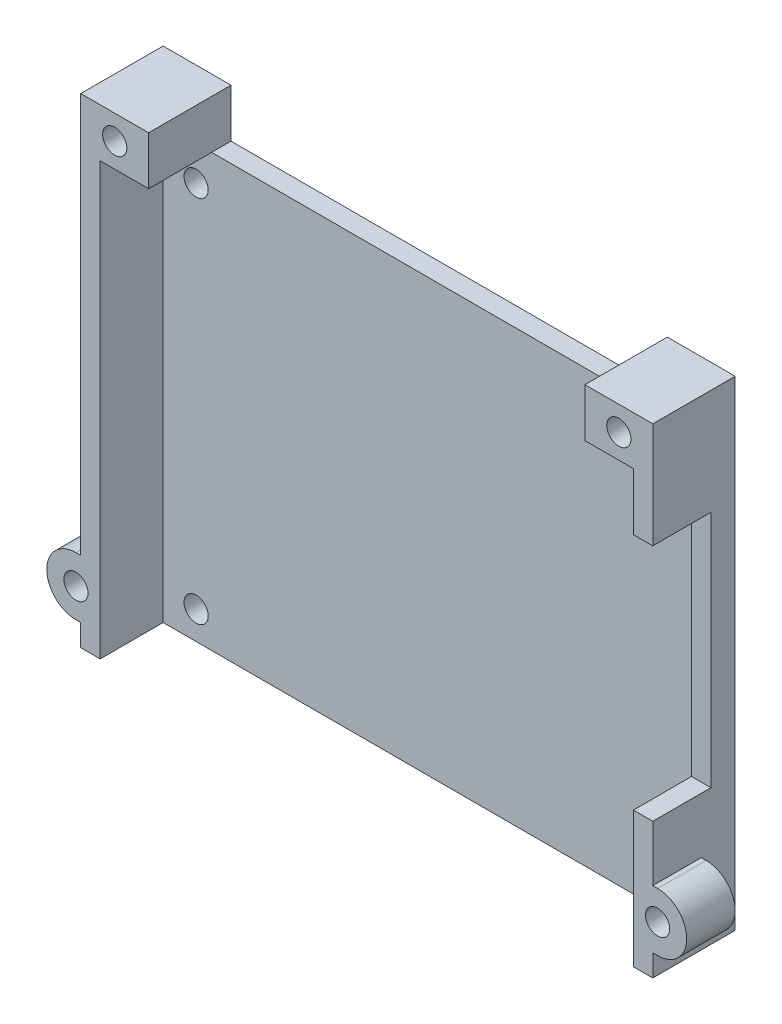
SolidWorks part; units mm, degrees
ref_plane "Front Plane" through (0, 0, 0) normal (0, 0, 1) x (1, 0, 0)
ref_plane "Top Plane" through (0, 0, 0) normal (0, 1, 0) x (1, 0, 0)
ref_plane "Right Plane" through (0, 0, 0) normal (1, 0, 0) x (0, 0, -1)
sketch "Sketch1" plane through (0, 0, 0) normal (0, 1, 0) x (1, 0, 0)
  line L0 (0, 0) -> (2, 0)
  line L1 (0, 0) -> (59, 0) construction
  line L2 (0, 0) -> (0, 8.5)
  line L3 (0, 8.5) -> (59, 8.5)
  line L4 (59, 0) -> (59, 8.5)
  line L5 (2, 0) -> (2, 6.5)
  line L6 (2, 6.5) -> (57, 6.5)
  line L7 (57, 6.5) -> (57, 0)
  line L8 (57, 0) -> (59, 0)
  dimension "D1" = 59
  dimension "D2" = 8.5
  dimension "D3" = 2
  dimension "D4" = 6.5
  dimension "D5" = 55
extrude "Boss-Extrude1" add sketch "Sketch1" along normal blind 44.5
sketch "Sketch2" plane through (59, 0, 0) normal (1, 0, 0) x (0, 0, -1)
  line L0 (0, 0) -> (0, 14) construction
  line L1 (0, 44.5) -> (0, 0) construction
  line L2 (0, 14) -> (6, 14)
  line L3 (6, 14) -> (6, 38.6)
  line L4 (6, 38.6) -> (0, 38.6)
  line L5 (0, 38.6) -> (0, 14)
  dimension "D1" = 14
  dimension "D2" = 6
  dimension "D3" = 24.6
extrude "Cut-Extrude1" cut sketch "Sketch2" against normal blind 10
sketch "Sketch3" plane through (0, 0, -8.5) normal (0, 0, -1) x (-1, 0, 0)
  line L0 (-59, 0) -> (-59, 8.25) construction
  line L1 (-59, 44.5) -> (-59, 0) construction
  line L2 (-59, 8.25) -> (-59, 2.25)
  line L3 (-59, 5.25) -> (-59.5, 5.25) construction
  line L4 (-59, 8.25) -> (-59.5, 8.25)
  line L5 (-59, 2.25) -> (-59.5, 2.25)
  line L6 (0, 0) -> (0, 8.25) construction
  line L7 (0, 44.5) -> (0, 0) construction
  line L8 (0, 8.25) -> (0.5, 8.25)
  line L9 (0, 8.25) -> (0, 2.25)
  line L10 (0, 2.25) -> (0.5, 2.25)
  line L11 (0, 5.25) -> (0.5, 5.25) construction
  arc A0 (-59.5, 8.25) -> (-59.5, 2.25) centre (-59.5, 5.25) ccw
  circle A1 centre (-59.5, 5.25) radius 1.25
  arc A2 (0.5, 8.25) -> (0.5, 2.25) centre (0.5, 5.25) cw
  circle A3 centre (0.5, 5.25) radius 1.25
  line M5 (0, 0) -> (0, 44.5)
  line M7 (-59, 44.5) -> (-59, 0)
  dimension "D4" = 3
  dimension "D5" = 2.5
  dimension "D11" = 3
  dimension "D12" = 2.5
  dimension "D1" = 8.25
  dimension "D2" = 6
  dimension "D3" = 0.5
  dimension "D6" = 8.25
  dimension "D7" = 0.5
  dimension "D8" = 6
  dimension "D9" = 0.5
extrude "Boss-Extrude2" add sketch "Sketch3" against normal blind 8.5 contours A1 L4 A0 L5 M7 | A3 L10 A2 L8 M5 region at (59.0695, 7.3228, -8.5) region at (-0.25, 8.1805, -8.5)
extrude "Cut-Extrude2" cut sketch "Sketch3<3>" against normal blind 11 contours L2 A1 | L9 A3 region at (58.6906, 5.25, -8.5) region at (0.3094, 5.25, -8.5)
sketch "Sketch3<3>" plane through (0, 0, -8.5) normal (0, 0, -1) x (-1, 0, 0) same geometry as "Sketch3"
sketch "Sketch4" plane through (0, 44.5, 0) normal (0, 1, 0) x (1, 0, 0)
  line L0 (59, 8.5) -> (0, 8.5) construction
  line L1 (0, 0) -> (7, 0)
  line L2 (0, 0) -> (0, 8.5)
  line L3 (0, 8.5) -> (7, 8.5)
  line L4 (7, 0) -> (7, 8.5)
  line L6 (59, 0) -> (52, 0)
  line L7 (59, 0) -> (59, 8.5)
  line L8 (59, 8.5) -> (52, 8.5)
  line L9 (52, 0) -> (52, 8.5)
  dimension "D1" = 7
  dimension "D2" = 7
extrude "Boss-Extrude3" add sketch "Sketch4" along normal blind 5
sketch "Sketch5" plane through (0, 0, -8.5) normal (0, 0, -1) x (-1, 0, 0)
  line L0 (-59, 49.5) -> (-52, 44.5) construction
  line L1 (0, 49.5) -> (-7, 44.5) construction
  circle A0 centre (-55.5, 47) radius 1.25
  circle A1 centre (-3.5, 47) radius 1.25
  dimension "D1" = 2.5
  dimension "D2" = 2.5
extrude "Cut-Extrude3" cut sketch "Sketch5" against normal through all
sketch "Sketch7" plane through (0, 0, -8.5) normal (0, 0, -1) x (-1, 0, 0)
  line L0 (-59, 0) -> (-59, 2.9) construction
  line L1 (-59, 2.25) -> (-59, 0) construction
  line L2 (-59, 2.9) -> (0, 2.9) construction
  line L3 (0, 2.25) -> (0, 0) construction
  line L4 (-53.6, 2.9) -> (-5.4, 2.9)
  line L5 (-53.6, 2.9) -> (-53.6, 40.95) construction
  line L6 (-53.6, 40.95) -> (-5.4, 40.95) construction
  circle A0 centre (-53.6, 2.9) radius 1.25
  circle A1 centre (-5.4, 2.9) radius 1.25
  circle A2 centre (-53.6, 40.95) radius 1.25
  circle A3 centre (-5.4, 40.95) radius 1.25
  point P11 (-29.5, 2.9)
  dimension "D3" = 2.5
  dimension "D4" = 2.5
  dimension "D6" = 2.5
  dimension "D8" = 2.5
  dimension "D1" = 2.9
  dimension "D2" = 48.2
  dimension "D5" = 38.05
  dimension "D7" = 48.2
extrude "Cut-Extrude4" cut sketch "Sketch7" against normal blind 10 contours A2 | A3 | A1 | A0 region at (5.4, 4.1146, -8.5) region at (54.8146, 2.9, -8.5) region at (53.6, 40.95, -8.5) region at (5.4, 40.95, -8.5)
extrude "Cut-Extrude6" cut sketch "Sketch3<4>" against normal blind 3.5 contours A1 L4 A0 L5 M7 | A3 L10 A2 L8 M5 region at (59.0695, 7.3228, -8.5) region at (-0.25, 8.1805, -8.5)
sketch "Sketch3<4>" plane through (0, 0, -8.5) normal (0, 0, -1) x (-1, 0, 0) same geometry as "Sketch3"
extrude "Boss-Extrude4" add sketch "Sketch3<5>" against normal blind 3 contours L9 A3 | L2 A1 region at (58.6906, 5.25, -8.5) region at (0.3094, 5.25, -8.5)
sketch "Sketch3<5>" plane through (0, 0, -8.5) normal (0, 0, -1) x (-1, 0, 0) same geometry as "Sketch3"
